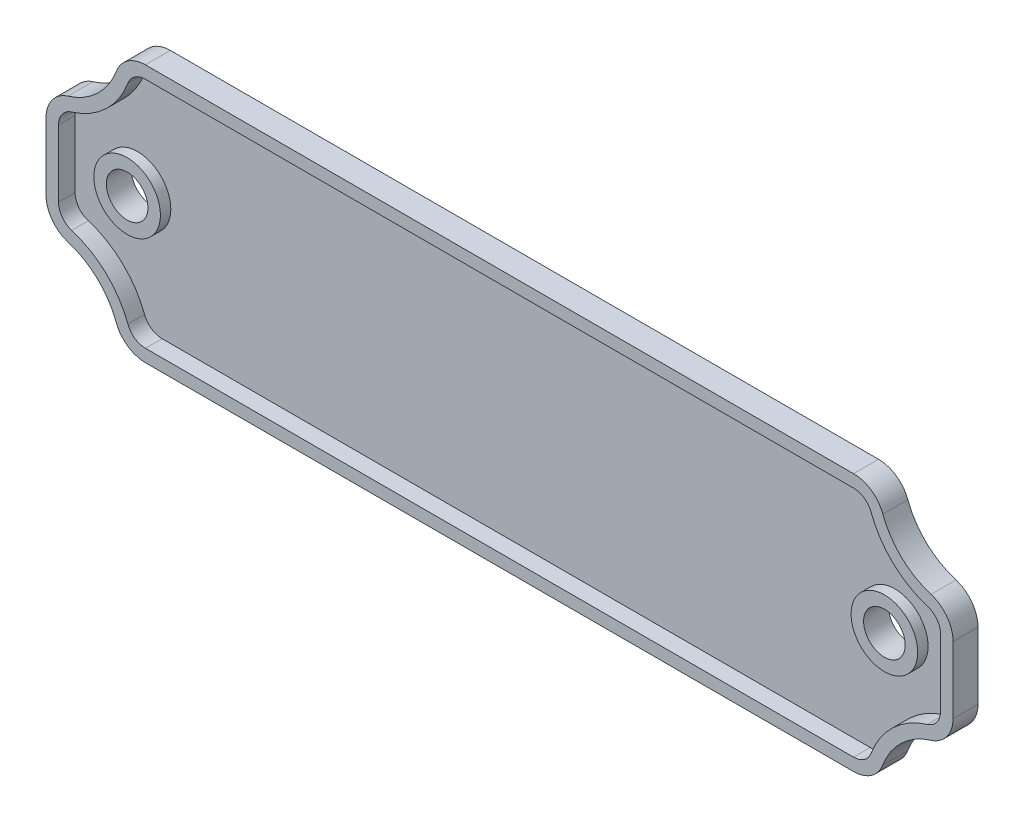
SolidWorks part; units mm, degrees
material "Brass"
ref_plane "Front Plane" through (0, 0, 0) normal (0, 0, 1) x (1, 0, 0)
ref_plane "Top Plane" through (0, 0, 0) normal (0, 1, 0) x (1, 0, 0)
ref_plane "Right Plane" through (0, 0, 0) normal (1, 0, 0) x (0, 0, -1)
sketch "Base Plate Sketch" plane through (0, 0, 0) normal (0, 0, 1) x (1, 0, 0)
  line L0 (-42.5498, 15.5) -> (42.5498, 15.5)
  line L1 (0, 33.6838) -> (0, -33.6838) construction
  line L2 (-42.5498, -15.5) -> (42.5498, -15.5)
  line L3 (54.5, 4.0085) -> (54.5, -4.0085)
  line L4 (-54.5, 4.0085) -> (-54.5, -4.0085)
  line L5 (-91.3272, 0) -> (91.3272, 0) construction
  line L6 (-54.5, 23.0463) -> (-54.5, -17.0186) construction
  line L7 (54.5, 22.0356) -> (54.5, -23.4922) construction
  arc A0 (-46.0645, 13.0572) -> (-51.8529, 7.5926) centre (-54.5, 16.1946) cw
  arc A1 (51.8529, 7.5926) -> (46.0645, 13.0572) centre (54.5, 16.1946) cw
  arc A2 (-46.0645, -13.0572) -> (-51.8529, -7.5926) centre (-54.5, -16.1946) ccw
  arc A3 (46.0645, -13.0572) -> (51.8529, -7.5926) centre (54.5, -16.1946) cw
  arc A4 (-51.8529, -7.5926) -> (-54.5, -4.0085) centre (-50.75, -4.0085) cw
  arc A5 (-54.5, 4.0085) -> (-51.8529, 7.5926) centre (-50.75, 4.0085) cw
  arc A6 (51.8529, -7.5926) -> (54.5, -4.0085) centre (50.75, -4.0085) ccw
  arc A7 (54.5, 4.0085) -> (51.8529, 7.5926) centre (50.75, 4.0085) ccw
  arc A8 (-42.5498, -15.5) -> (-46.0645, -13.0572) centre (-42.5498, -11.75) cw
  arc A9 (42.5498, -15.5) -> (46.0645, -13.0572) centre (42.5498, -11.75) ccw
  arc A10 (46.0645, 13.0572) -> (42.5498, 15.5) centre (42.5498, 11.75) ccw
  arc A11 (-42.5498, 15.5) -> (-46.0645, 13.0572) centre (-42.5498, 11.75) ccw
  point P38 (-54.5, 0)
  point P39 (54.5, 0)
  point P40 (0, 0)
  point P45 (0, 0)
  point P53 (54.5, -7.1946)
  point P56 (54.5, 7.1946)
  point P72 (0, 15.5)
  dimension "D3" = 31
  dimension "D4" = 14.3891
  dimension "D1" = 9
  dimension "D5" = 3.75
  dimension "D2" = 109
  dimension "D6" = 15.5
extrude "Name Plate Bezel" add sketch "Base Plate Sketch" along normal blind 3 thin contours L0 A11 A0 A5 L4 A4 A2 A8 L2 A9 A3 A6 L3 A7 A1 A10 thin type one direction reverse wall 1.5
extrude "Name Plate Backplate" add sketch "Sketch1<6>" along normal blind 1 contours L0 A11 A0 A5 L4 A4 A2 A8 L2 A9 A3 A6 L3 A7 A1 A10 region at (0, 0, 0)
sketch "Sketch1<6>" plane through (0, 0, 0) normal (0, 0, 1) x (1, 0, 0) same geometry as "Base Plate Sketch"
sketch "Hole Sketch" plane through (0, 0, 0) normal (0, 0, 1) x (1, 0, 0)
  line L0 (0, 23.2689) -> (0, -27.054) construction
  line L1 (-54.5, 0) -> (54.5, 0) construction
  line L2 (-54.5, 4.0085) -> (-54.5, -4.0085) construction
  line L3 (54.5, 4.0085) -> (54.5, -4.0085) construction
  circle A0 centre (-45.5, 0) radius 2.5
  circle A1 centre (-45.5, 0) radius 4
  circle A2 centre (45.5, 0) radius 2.5
  circle A3 centre (45.5, 0) radius 4
  point P6 (0, 0)
  dimension "D1" = 5
  dimension "D2" = 8
  dimension "D3" = 9
extrude "Hole Bezel" add sketch "Hole Sketch" against normal blind 0.75 and the other way blind 2.25 from surface contours A3 A2 | A1 A0 region at (-49.3869, 0, 0) region at (41.6131, 0, 0) starting at face at (0, 0, 0)
extrude "Hole Cutout" cut sketch "Hole Sketch<6>" against normal through all and the other way through all contours A0 | A2 region at (-45.5, 0, 0)
sketch "Hole Sketch<6>" plane through (0, 0, 0) normal (0, 0, 1) x (1, 0, 0) same geometry as "Hole Sketch"
